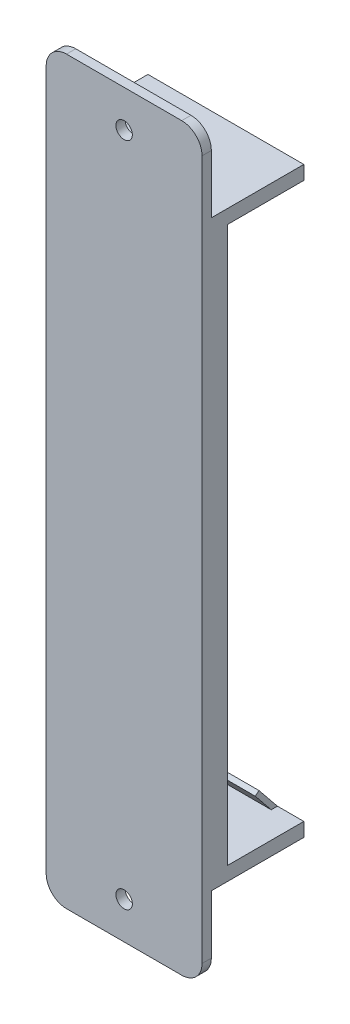
SolidWorks part; units mm, degrees
ref_plane "Front Plane" through (0, 0, 0) normal (0, 0, 1) x (1, 0, 0)
ref_plane "Top Plane" through (0, 0, 0) normal (0, 1, 0) x (1, 0, 0)
ref_plane "Right Plane" through (0, 0, 0) normal (1, 0, 0) x (0, 0, -1)
sketch "Sketch2" plane through (0, 0, 0) normal (0, 1, 0) x (1, 0, 0)
  line L0 (-6.5522, -8.4597) -> (-10.7004, -8.4597)
  line L1 (-10.7004, -8.4597) -> (-10.7004, -10.7004)
  line L2 (-10.7004, -10.7004) -> (10.7004, -10.7004)
  line L3 (10.7004, -10.7004) -> (10.7004, -8.4597)
  line L4 (10.7004, -8.4597) -> (6.5522, -8.4597)
  line L5 (-10.7004, -10.7004) -> (-10.7004, -11.9704)
  line L6 (-10.7004, -11.9704) -> (10.7004, -11.9704)
  line L7 (10.7004, -11.9704) -> (10.7004, -10.7004)
  circle A0 centre (0, 0) radius 10.7004
  dimension "D1" = 21.4008
  dimension "D2" = 1.27
extrude "Boss-Extrude3" add sketch "Sketch2" against normal blind 88.9 and the other way blind 12.7 contours L6 L7 L2 L5 region at (0, 0, 11.3354)
extrude "Boss-Extrude4" add sketch "Sketch2<3>" against normal blind 76.2 contours A0 L0 L1 L2 | A0 L2 L3 L4 region at (-7.3973, 0, 9.7346) region at (7.3973, 0, 9.7346)
sketch "Sketch2<3>" plane through (0, 0, 0) normal (0, 1, 0) x (1, 0, 0) same geometry as "Sketch2"
sketch "Sketch3" plane through (0, 0, 10.7004) normal (0, 0, -1) x (-1, 0, 0)
  line L0 (-10.7004, 0) -> (10.7004, 0)
  line L1 (10.7004, 0) -> (10.7004, 1.905)
  line L2 (10.7004, 12.7) -> (10.7004, 0) construction
  line L3 (10.7004, 1.905) -> (-10.7004, 1.905)
  line L4 (-10.7004, 12.7) -> (-10.7004, 0) construction
  line L5 (-10.7004, 1.905) -> (-10.7004, 0)
  dimension "D1" = 1.905
extrude "Boss-Extrude5" add sketch "Sketch3" along normal blind 12.7
sketch "Sketch4" plane through (0, 0, 10.7004) normal (0, 0, -1) x (-1, 0, 0)
  line L0 (-10.7004, -76.2) -> (10.7004, -76.2)
  line L1 (10.7004, -76.2) -> (10.7004, -78.105)
  line L2 (10.7004, -76.2) -> (10.7004, -88.9) construction
  line L3 (10.7004, -78.105) -> (-10.7004, -78.105)
  line L4 (-10.7004, -76.2) -> (-10.7004, -88.9) construction
  line L5 (-10.7004, -78.105) -> (-10.7004, -76.2)
  dimension "D1" = 1.905
extrude "Boss-Extrude6" add sketch "Sketch4" along normal blind 12.7
sketch "Sketch5" plane through (10.7004, 0, 0) normal (1, 0, 0) x (0, 0, -1)
  line L0 (1.9818, 0) -> (1.9818, -3.0962)
  line L1 (10.7004, 0) -> (-10.7004, 0) construction
  line L2 (1.9818, 0) -> (-1.2044, -3.1861)
  line L3 (0.6807, 0) -> (-1.9711, -2.6517)
  line L4 (0.6807, 0) -> (1.9818, 0)
  line L5 (-1.9711, -2.6517) -> (-1.2044, -3.1861)
  line M7 (-8.4597, 0) -> (1.9996, 0)
  dimension "D1" = 3.0962
extrude "Boss-Extrude7" add sketch "Sketch5" against normal blind 17.78 contours L3 L5 L2 M7 region at (10.7004, -1.4635, 0.1125)
extrude "Cut-Extrude1" cut sketch "Sketch5<4>" against normal blind 3.556 contours L3 L5 L2 M7 region at (10.7004, -1.4635, 0.1125)
sketch "Sketch5<4>" plane through (10.7004, 0, 0) normal (1, 0, 0) x (0, 0, -1) same geometry as "Sketch5"
sketch "Sketch6" plane through (-10.7004, 0, 0) normal (-1, 0, 0) x (0, 0, 1)
  line L0 (-1.9996, -76.2) -> (-1.9996, -73.074)
  line L1 (-1.9996, -76.2) -> (0.5305, -73.074)
  line L2 (0.5305, -73.074) -> (1.0468, -73.4919)
  line L3 (1.0468, -73.4919) -> (-1.1452, -76.2)
  line L4 (-1.9996, -76.2) -> (8.4597, -76.2) construction
  line L5 (-1.9996, -76.2) -> (-1.1452, -76.2)
  line M11 (8.4597, -76.2) -> (-1.9996, -76.2)
extrude "Boss-Extrude8" add sketch "Sketch6" against normal blind 17.78 contours L3 L2 L1 M11 region at (-10.7004, -74.739, -0.4)
extrude "Cut-Extrude2" cut sketch "Sketch6<3>" against normal blind 3.556 contours L3 L2 L1 M11 region at (-10.7004, -74.739, -0.4)
sketch "Sketch6<3>" plane through (-10.7004, 0, 0) normal (-1, 0, 0) x (0, 0, 1) same geometry as "Sketch6"
sketch "Sketch7" plane through (0, 0, 10.7004) normal (0, 0, -1) x (-1, 0, 0)
  line L0 (10.7004, 12.7) -> (-10.7004, 12.7) construction
  line L1 (10.7004, -88.9) -> (-10.7004, -88.9) construction
  point P1 (0, 7.62)
  point P4 (0, -83.82)
  dimension "D1" = 5.08
  dimension "D2" = 5.08
hole_wizard "#4-40 Tapped Hole1" positions "Sketch7" profile "Sketch8" tap size "#4-40" standard "ANSI Inch"
sketch "Sketch8" plane through (0, -83.82, 10.7004) normal (1, 0, 0) x (0, 1, 0)
  line L0 (0, 0) -> (0, 8.2992)
  line L1 (0, 8.2992) -> (1.1303, 7.62)
  line L2 (1.1303, 7.62) -> (1.1303, 0)
  line L5 (1.1303, 0) -> (0, 0)
  line L10 (0, 8.2992) -> (-1.1303, 7.62) construction
  line L11 (0, -6.35) -> (0, 107.95) construction
  dimension "Tap Drill Dia." = 2.2606
  dimension "Tap Drill Depth" = 7.62
  dimension "Drill Angle" = 118
cosmetic thread "Hole Thread1" parameters "D1"=5.588, "D2"=2.8448
cosmetic thread "Hole Thread2" parameters "D1"=5.588, "D2"=2.8448
fillet "Fillet1" radius 2.794 4 edges at (-10.7004, -88.9, 11.3354) (10.7004, -88.9, 11.3354) (-10.7004, 12.7, 11.3354) (10.7004, 12.7, 11.3354)
